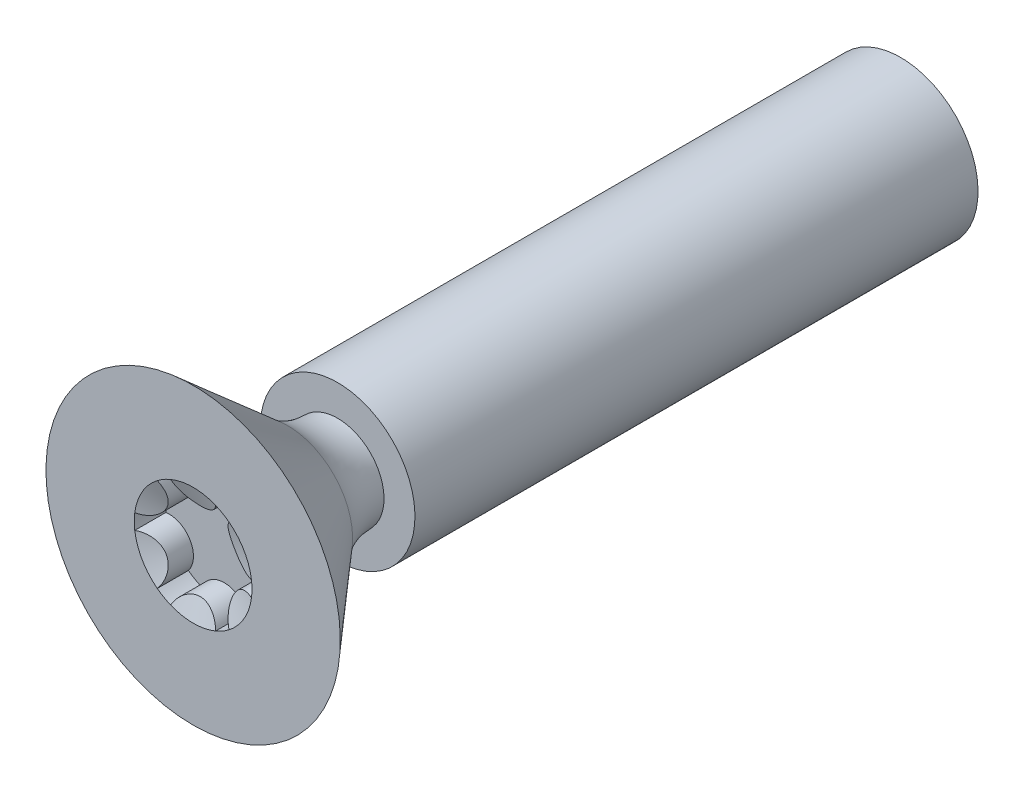
SolidWorks part; units mm, degrees
material "Plain Carbon Steel"
ref_plane "Front Plane" through (0, 0, 0) normal (0, 0, 1) x (1, 0, 0)
ref_plane "Top Plane" through (0, 0, 0) normal (0, 1, 0) x (1, 0, 0)
ref_plane "Right Plane" through (0, 0, 0) normal (1, 0, 0) x (0, 0, -1)
sketch "Sketch1" plane through (0, 0, 0) normal (1, 0, 0) x (0, 0, -1)
  line L0 (-9.525, 0) -> (9.525, 0) construction
  line L1 (9.525, 0) -> (9.525, 2.0828) construction
  line L2 (9.525, 2.0828) -> (-6.985, 2.0828) construction
  line L4 (-9.525, 3.9624) -> (-9.525, 0) construction
  line L5 (9.525, -2.0828) -> (9.525, 2.0828) construction
  line L6 (9.4258, 2.2547) -> (10.2195, 0.8798) construction
  line L7 (10.2195, 0.8798) -> (11.0133, 2.2547) construction
  line L8 (11.0133, 2.2547) -> (9.4258, 2.2547) construction
  line L9 (10.2195, 0.8798) -> (10.2195, 1.0517) construction
  line L10 (10.2195, 2.2547) -> (10.2195, 2.0828) construction
  line L11 (10.9141, 2.0828) -> (9.525, 2.0828) construction
  line L12 (10.2195, 2.1687) -> (10.9637, 2.1687) construction
  line L13 (10.2195, 2.1687) -> (9.4754, 2.1687) construction
  line L14 (10.1203, 1.0517) -> (10.3188, 1.0517) construction
  line L15 (-9.525, 3.9624) -> (-6.985, 1.0405) construction
  line L16 (7.1438, 2.0828) -> (7.1438, 0) construction
  line L17 (7.1438, 2.0828) -> (7.9375, 1.9428) construction
  line L18 (7.9375, 1.9428) -> (8.7313, 1.8029) construction
  line L19 (8.7313, 1.8029) -> (9.525, 1.6629) construction
  line L20 (-9.525, 1.0405) -> (-6.985, 1.0405) construction
  line L21 (-6.985, 2.0828) -> (-6.985, 1.0405) construction
  line L22 (-7.1669, 1.2497) -> (7.1438, 1.2497) construction
  line L23 (-9.525, 3.9624) -> (-6.4044, 1.2497) construction
  line L24 (10.006, 1.2497) -> (10.4331, 1.2497) construction
  line L25 (-6.1913, 2.0828) -> (-7.0244, 1.2497) construction
  line L26 (-9.525, 2.1336) -> (-7.1374, 0) construction
  line L27 (-9.525, 0.3683) -> (-7.5495, 0.3683) construction
  line L28 (-6.4044, 1.2497) -> (-4.9668, 0) construction
  line L30 (-5.635, 0) -> (-5.635, 2.0828) construction
  line L31 (-4.4444, 0) -> (-4.4444, 2.0828) construction
  arc A1 (-7.2862, 1.3869) -> (-6.985, 1.2497) centre (-6.985, 1.6488) ccw construction
  arc A2 (-6.985, 1.7544) -> (-5.635, 1.2497) centre (-5.635, 3.3074) ccw construction
  point P0 (4.7625, 2.0828)
  point P4 (0, 0)
  point P10 (9.525, 0)
  point P41 (-6.736, 1.538)
  point P45 (-9.525, 1.585)
  point P55 (-8.763, 1.0405)
  dimension "Length" = 19.05
  dimension "Screw OD" = 4.1656
  dimension "Head DIa" = 7.9248
  dimension "Pitch" = 1.5875
  dimension "D2" = 0.1984
  dimension "D3" = 41
  dimension "D4" = 10
  dimension "D5" = 1.5875
  dimension "Head Ht" = 2.54
  dimension "D6" = 0.8331
  dimension "D1" = 4.7625
  dimension "D7" = 49
  dimension "D8" = 45
  dimension "D9" = 0.7937
  dimension "D10" = 3.1699
  dimension "Recess Wd" = 0.7366
  dimension "Recess Dia" = 4.2672
  dimension "Recess Dp" = 2.3876
  dimension "D11" = 1.1906
  dimension "D12" = 0.762
sketch "Sketch2" plane through (0, 0, 0) normal (0, 0, 1) x (1, 0, 0)
  line L0 (0, 0) -> (1.8038, -1.0414) construction
  line L1 (0, 0) -> (-1.8038, -1.0414) construction
  line L2 (0, 0.8798) -> (0, 2.2547) construction
  line L5 (0, 3.9624) -> (0, 0) construction
  line L12 (0, 0) -> (0.7925, 1.3726) construction
  line L13 (0, 0) -> (-0.7925, 1.3726) construction
  line L14 (0, 0) -> (-0.6065, 1.4643) construction
  line L15 (0, 0) -> (0.6065, 1.4643) construction
  line L17 (0, -2.0828) -> (0, 2.0828) construction
  circle A7 centre (0, 0) radius 2.0828 construction
  circle A9 centre (0, 0) radius 1.585 construction
  arc A10 (-0.6065, 1.4643) -> (0.6065, 1.4643) centre (0, 1.7155) ccw construction
  arc A11 (-0.4207, 1.9688) -> (0.4207, 1.9688) centre (0, 1.2497) cw construction
  arc A12 (-1.9154, -0.62) -> (-1.4946, -1.3488) centre (-1.0823, -0.6248) ccw construction
  arc A13 (1.9154, -0.62) -> (1.4946, -1.3488) centre (1.0823, -0.6248) cw construction
  arc A14 (-1.9154, -0.62) -> (-0.4207, 1.9688) centre (1.1043, -0.6375) cw construction
  arc A15 (0.4207, 1.9688) -> (1.9154, -0.62) centre (-1.1043, -0.6375) cw construction
  arc A16 (1.4946, -1.3488) -> (-1.4946, -1.3488) centre (0, 1.2751) cw construction
  circle A17 centre (0, 0) radius 1.2497 construction
  point P0 (0, 3.9624)
  point P17 (1.8038, -1.0414)
  point P19 (-1.8038, -1.0414)
  point P21 (0, 1.2497)
  point P22 (1.8038, -1.0414)
  point P25 (0, -1.7446)
  point P26 (-1.8038, -1.0414)
  point P29 (0, 2.0828)
  point P66 (-1.0823, -0.6248)
  dimension "D1" = 0.8331
  dimension "D2" = 120
  dimension "D3" = 120
  dimension "D6" = 7.5
  dimension "D7" = 7.5
  dimension "D8" = 30
  dimension "D9" = 30
  dimension "D4" = 0.0254
sketch "Sketch3" plane through (0, 0, 0) normal (1, 0, 0) x (0, 0, -1)
  line L0 (9.525, 0) -> (9.525, 2.0828) construction
  line L1 (-9.525, 0) -> (9.525, 0) construction
  line L2 (9.525, 2.0828) -> (-6.985, 2.0828) construction
  line L3 (-5.635, 2.0828) -> (-5.635, 1.2497)
  line L4 (-9.525, 3.9624) -> (-9.525, 0) construction
  line L5 (9.525, 0) -> (9.525, 2.0828)
  line L6 (-9.525, 0) -> (9.525, 0)
  line L7 (9.525, 2.0828) -> (-5.635, 2.0828)
  line L9 (-9.525, 3.9624) -> (-9.525, 0)
  line L15 (-9.525, 3.9624) -> (-6.4044, 1.2497) construction
  line L17 (-9.525, 3.9624) -> (-6.985, 1.7544)
  arc A0 (-6.985, 1.7544) -> (-5.635, 1.2497) centre (-5.635, 3.3074) ccw construction
  arc A1 (-6.985, 1.7544) -> (-5.635, 1.2497) centre (-5.635, 3.3074) ccw
revolve "Revolve1" add sketch "Sketch3" angle 360 about L0
ref_plane "Plane1" through (0, 0, 9.525) normal (0, 0, 1) x (1, 0, 0)
ref_plane "Plane5" through (0, 0, -7.1438) normal (0, 0, 1) x (1, 0, 0)
ref_plane "Plane6" through (0, 0, 5.635) normal (0, 0, 1) x (1, 0, 0)
ref_plane "Plane7" through (0, 0, 4.4444) normal (0, 0, 1) x (1, 0, 0)
sketch "Sketch21" plane through (0, 0, 9.525) normal (0, 0, 1) x (1, 0, 0)
  line L0 (0, 0) -> (-0.7925, 1.3726) construction
  line L3 (0, 0) -> (0.7925, 1.3726) construction
  line L4 (0, 0) -> (-0.7925, 1.3726)
  line L7 (0, 0) -> (0.7925, 1.3726)
  circle A0 centre (0, 0) radius 1.585 construction
  arc A1 (-0.6065, 1.4643) -> (0.6065, 1.4643) centre (0, 1.7155) ccw construction
  arc A2 (0.7925, 1.3726) -> (0.6065, 1.4643) centre (0, 0) ccw
  arc A3 (-0.6065, 1.4643) -> (0.6065, 1.4643) centre (0, 1.7155) ccw
  arc A4 (-0.6065, 1.4643) -> (-0.7925, 1.3726) centre (0, 0) ccw
extrude "Cut-Extrude14" cut sketch "Sketch21" against normal blind 0.8382
pattern_circular "CirPattern1" count 6 over 360 about axis through (0, 0, 9.525) along (0, 0, -1) of "Cut-Extrude14"
sketch "Sketch22" plane through (0, 0, 9.525) normal (0, 0, 1) x (1, 0, 0)
  circle A0 centre (0, 0) radius 1.585 construction
  circle A1 centre (0, 0) radius 1.585
extrude "Cut-Extrude15" cut sketch "Sketch22" against normal up to vertex (0.762 mm away) draft 70 up to point (0, 1.0405, 8.763)
sketch "Sketch20" plane through (0, 0, 0) normal (1, 0, 0) x (0, 0, -1)
  line L0 (9.525, -2.0828) -> (9.525, 2.0828) construction
  point P0 (7.1438, -1.7446)
  dimension "D1" = 2.3813
sketch "Sketch24" plane through (0, 0, 9.525) normal (0, 0, 1) x (1, 0, 0)
  circle A0 centre (0, 0) radius 3.9624
  point P0 (0.9649, -1.2574)
ref_axis "Center Axis 1" through (0, 0, 9.525) along (0, 0, -1)
ref_plane "Contact Plane 1" through (0, 0, -9.525) normal (0, 0, -1) x (-1, 0, 0)
ref_plane "Contact Plane 2" through (0, 0, 6.985) normal (0, 0, 1) x (1, 0, 0)
sketch "Sketch8" [suppressed] plane through (0, 0, -9.525) normal (0, 0, -1) x (-1, 0, 0)
  line L0 (0, -2.0828) -> (0, 2.0828) construction
  circle A0 centre (0, 0) radius 2.0828
  point P0 (0, 2.0828)
curve "Helix/Spiral1" [suppressed] pitch 1.5875 height 18.0975 turns 11.4
split "Split1" [suppressed] bodies to split 147
sketch "Sketch9" [suppressed] plane through (0, 0, 0) normal (1, 0, 0) x (0, 0, -1)
  line L0 (9.4754, 2.1687) -> (10.006, 1.2497)
  line L2 (10.4331, 1.2497) -> (10.9637, 2.1687)
  line L3 (9.4754, 2.1687) -> (10.9637, 2.1687)
  line L5 (10.006, 1.2497) -> (10.4331, 1.2497)
sweep "Cut-Sweep1" [suppressed] cut profiles "Sketch9" path "Helix/Spiral1"
sketch "Sketch11" [suppressed] plane through (0, 0, 5.635) normal (0, 0, 1) x (1, 0, 0)
  arc A0 (1.4946, -1.3488) -> (1.9154, -0.62) centre (1.0823, -0.6248) ccw construction
  arc A1 (-1.4946, -1.3488) -> (1.4946, -1.3488) centre (0, 1.2751) ccw construction
  arc A2 (-1.9154, -0.62) -> (-1.4946, -1.3488) centre (-1.0823, -0.6248) ccw construction
  arc A3 (-0.4207, 1.9688) -> (-1.9154, -0.62) centre (1.1043, -0.6375) ccw construction
  arc A4 (0.4207, 1.9688) -> (-0.4207, 1.9688) centre (0, 1.2497) ccw construction
  arc A5 (1.9154, -0.62) -> (0.4207, 1.9688) centre (-1.1043, -0.6375) ccw construction
  arc A6 (1.4946, -1.3488) -> (1.9154, -0.62) centre (1.0823, -0.6248) ccw
  arc A7 (-1.4946, -1.3488) -> (1.4946, -1.3488) centre (0, 1.2751) ccw
  arc A8 (-1.9154, -0.62) -> (-1.4946, -1.3488) centre (-1.0823, -0.6248) ccw
  arc A9 (-0.4207, 1.9688) -> (-1.9154, -0.62) centre (1.1043, -0.6375) ccw
  arc A10 (0.4207, 1.9688) -> (-0.4207, 1.9688) centre (0, 1.2497) ccw
  arc A11 (1.9154, -0.62) -> (0.4207, 1.9688) centre (-1.1043, -0.6375) ccw
extrude "Cut-Extrude3" [suppressed] cut sketch "Sketch11" against normal through all flip side to cut
sketch "Sketch18" [suppressed] plane through (0, 0, 4.4444) normal (0, 0, 1) x (1, 0, 0)
  circle A0 centre (0, 0) radius 2.0828
  point P0 (0, 2.0828)
extrude "Cut-Extrude13" [suppressed] cut sketch "Sketch18" along normal through all draft 35.5 flip side to cut draft outward yes
sketch "Sketch12" [suppressed] plane through (0, 0, -7.1438) normal (0, 0, 1) x (1, 0, 0)
  arc A0 (-1.9154, -0.62) -> (-1.4946, -1.3488) centre (-1.0823, -0.6248) ccw construction
  arc A1 (-1.4946, -1.3488) -> (1.4946, -1.3488) centre (0, 1.2751) ccw construction
  arc A2 (1.4946, -1.3488) -> (1.9154, -0.62) centre (1.0823, -0.6248) ccw construction
  arc A3 (1.9154, -0.62) -> (0.4207, 1.9688) centre (-1.1043, -0.6375) ccw construction
  arc A4 (0.4207, 1.9688) -> (-0.4207, 1.9688) centre (0, 1.2497) ccw construction
  arc A5 (-0.4207, 1.9688) -> (-1.9154, -0.62) centre (1.1043, -0.6375) ccw construction
  arc A6 (-1.9154, -0.62) -> (-1.4946, -1.3488) centre (-1.0823, -0.6248) ccw
  arc A7 (-1.4946, -1.3488) -> (1.4946, -1.3488) centre (0, 1.2751) ccw
  arc A8 (1.4946, -1.3488) -> (1.9154, -0.62) centre (1.0823, -0.6248) ccw
  arc A9 (1.9154, -0.62) -> (0.4207, 1.9688) centre (-1.1043, -0.6375) ccw
  arc A10 (0.4207, 1.9688) -> (-0.4207, 1.9688) centre (0, 1.2497) ccw
  arc A11 (-0.4207, 1.9688) -> (-1.9154, -0.62) centre (1.1043, -0.6375) ccw
extrude "Cut-Extrude4" [suppressed] cut sketch "Sketch12" against normal through all draft 7 flip side to cut draft outward yes
sketch "Sketch15" [suppressed] plane through (0, 0, 0) normal (1, 0, 0) x (0, 0, -1)
  line L14 (-4.2985, 0) -> (-5.635, 0)
  line L17 (-5.635, 0) -> (-5.635, 1.2497)
  line L18 (-5.635, 1.2497) -> (-4.2985, 1.2497)
  line L19 (-7.1669, 1.2497) -> (7.1438, 1.2497) construction
  line L20 (-4.2985, 1.2497) -> (-4.2985, 0)
  point P3 (-4.9668, 0)
revolve "Revolve3" [suppressed] add sketch "Sketch15" angle 360 about L0
equation "\"D2@Sketch1\"=\"Pitch@Sketch1\"/8"
equation "\"D5@Sketch1\"=\"Pitch@Sketch1\""
equation "\"D6@Sketch1\"=\"Screw OD@Sketch1\"*.2"
equation "\"D9@Sketch1\"=\"Pitch@Sketch1\"*.5"
equation "\"D1@Sketch1\"=\"Pitch@Sketch1\"*3"
equation "\"D1@Sketch2\"=\"Screw OD@Sketch1\"*.2"
equation "\"D4@Helix/Spiral1\"=\"Pitch@Sketch1\""
equation "\"D3@Helix/Spiral1\"=\"Length@Sketch1\"-\"Head Ht@Sketch1\"+\"Pitch@Sketch1\""
equation "\"D10@Sketch1\"=\"Head DIa@Sketch1\"*.4"
equation "\"D11@Sketch1\"=\"Pitch@Sketch1\"*.75"
equation "\"D1@Sketch20\"=\"Pitch@Sketch1\"*1.5"
equation "\"D1@Cut-Extrude14\"=\"Head Ht@Sketch1\"*.33"
equation "\"D12@Sketch1\"=\"Head Ht@Sketch1\"*.3"
